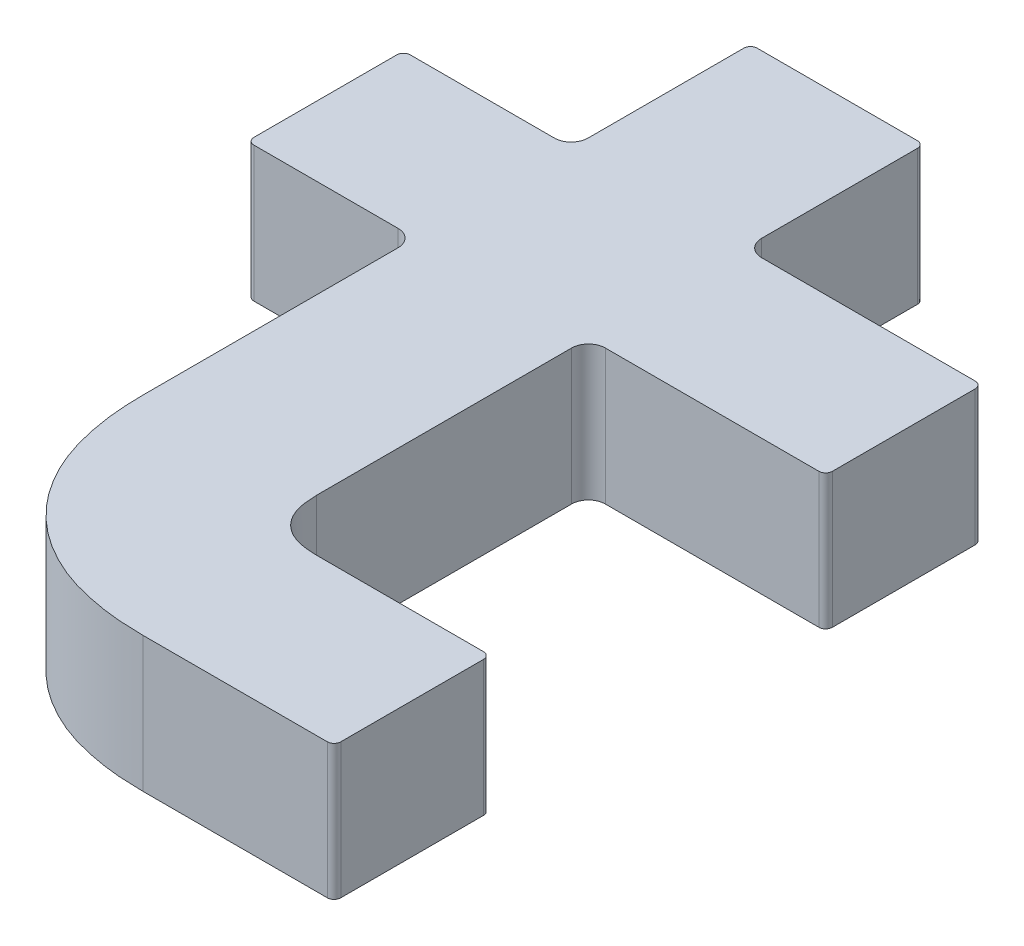
SolidWorks part; units mm, degrees
ref_plane "Front Plane" through (0, 0, 0) normal (0, 0, 1) x (1, 0, 0)
ref_plane "Top Plane" through (0, 0, 0) normal (0, 1, 0) x (1, 0, 0)
ref_plane "Right Plane" through (0, 0, 0) normal (1, 0, 0) x (0, 0, -1)
sketch "Sketch1" plane through (0, 0, 0) normal (0, 1, 0) x (1, 0, 0)
  text T0 "t" font "JetBrains Mono ExtraBold" height 125
extrude "Boss-Extrude1" add sketch "Sketch1" against normal blind 20
fillet "Fillet1" radius 2.5 4 edges at (30.8165, -10, -71.0464) (30.8165, -10, -94.1835) (56.5052, -10, -94.1835) (56.5052, -10, -71.0464)
fillet "Fillet2" radius 1 8 edges at (89.8979, -10, 0) (89.8979, -10, -23.1124) (5.9948, -10, -71.0464) (5.9948, -10, -94.1835) (30.8165, -10, -120.7144) (56.5052, -10, -120.7144) (91.6072, -10, -94.1835) (91.6072, -10, -71.0464)
